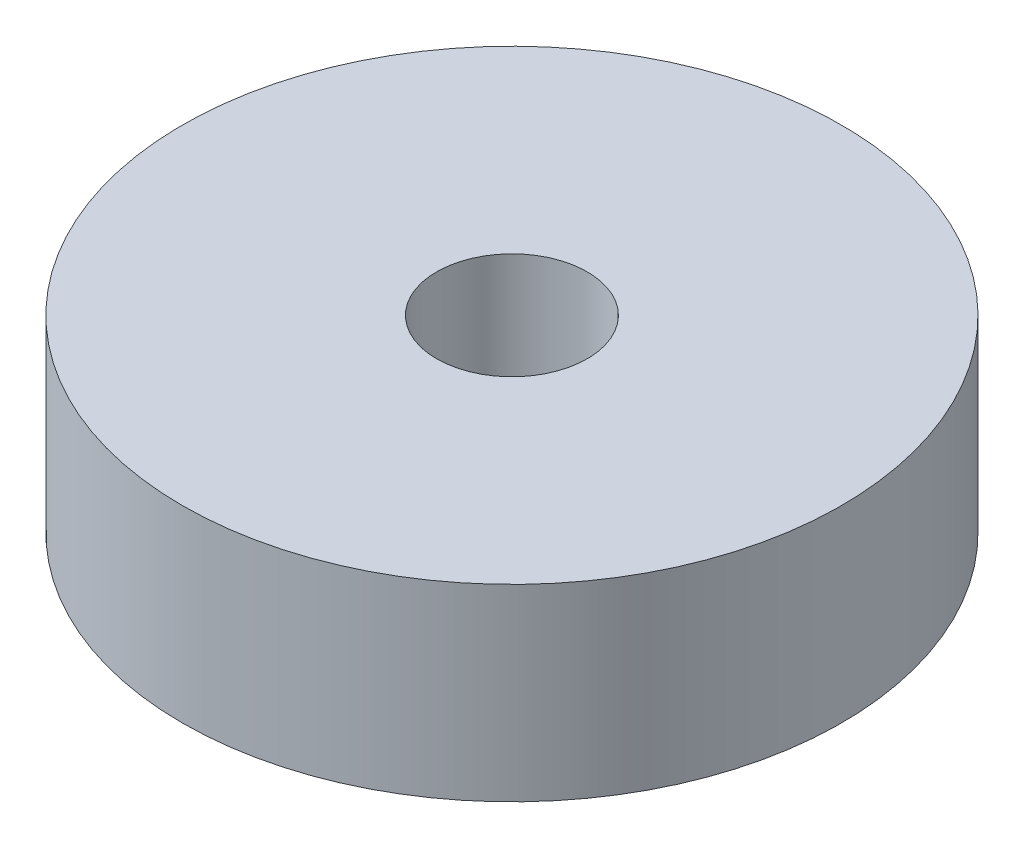
SolidWorks part; units mm, degrees
ref_plane "Front Plane" through (0, 0, 0) normal (0, 0, 1) x (1, 0, 0)
ref_plane "Top Plane" through (0, 0, 0) normal (0, 1, 0) x (1, 0, 0)
ref_plane "Right Plane" through (0, 0, 0) normal (1, 0, 0) x (0, 0, -1)
sketch "Sketch1" plane through (0, 0, 0) normal (0, 1, 0) x (1, 0, 0)
  circle A0 centre (0, 0) radius 17.5
  circle A1 centre (0, 0) radius 4
  dimension "D1" = 8
  dimension "D2" = 35
extrude "Boss-Extrude1" add sketch "Sketch1" along normal blind 10
sketch "Sketch3" plane through (0, 0, 0) normal (0, 1, 0) x (1, 0, 0)
  line L5 (-8.5, 3.3205) -> (-8.5, -3.3205)
  line L6 (-14.5, 3.3205) -> (-14.5, -3.3205)
  arc A3 (-14.5, 3.3205) -> (-8.5, 3.3205) centre (-11.5, 0) cw
  arc A4 (-14.5, -3.3205) -> (-8.5, -3.3205) centre (-11.5, 0) ccw
  dimension "D3" = 11.5
  dimension "D2" = 4.475
  dimension "D1" = 6
extrude "Cut-Extrude1" cut sketch "Sketch3" along normal blind 7
ref_plane "Plane1" through (-14.5, 0, 0) normal (1, 0, 0) x (0, 0, -1)
sketch "Sketch4" plane through (-14.5, 0, 0) normal (1, 0, 0) x (0, 0, -1)
  line L0 (3.3205, 0) -> (-3.3205, 0) construction
  circle A0 centre (0, 3) radius 2.125
  dimension "D1" = 3
  dimension "D2" = 4.25
extrude "Cut-Extrude2" cut sketch "Sketch4" against normal through all
